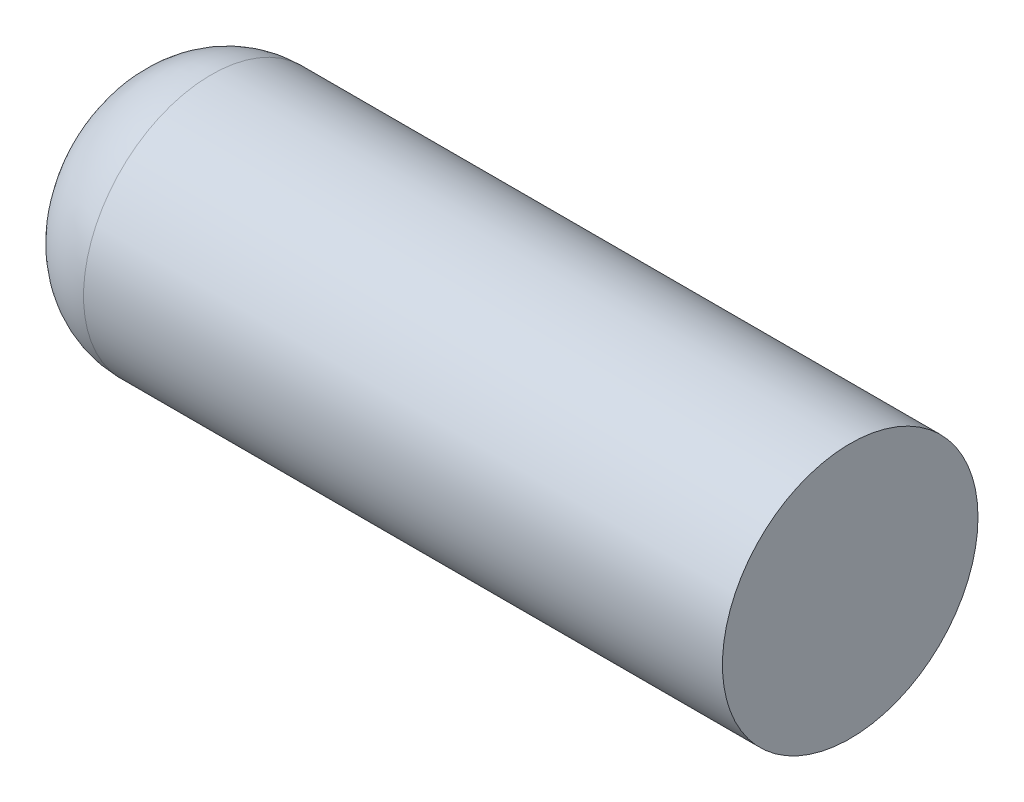
SolidWorks part; units mm, degrees
ref_plane "Front Plane" through (0, 0, 0) normal (0, 0, 1) x (1, 0, 0)
ref_plane "Top Plane" through (0, 0, 0) normal (0, 1, 0) x (1, 0, 0)
ref_plane "Right Plane" through (0, 0, 0) normal (1, 0, 0) x (0, 0, -1)
sketch "Sketch1" plane through (0, 0, 0) normal (1, 0, 0) x (0, 0, -1)
  circle A0 centre (0, 0) radius 1.4
  dimension "D1" = 2.8
extrude "Boss-Extrude1" add sketch "Sketch1" against normal blind 8
fillet "Fillet1" radius 1 1 edges at (-8, 0, -1.4)
